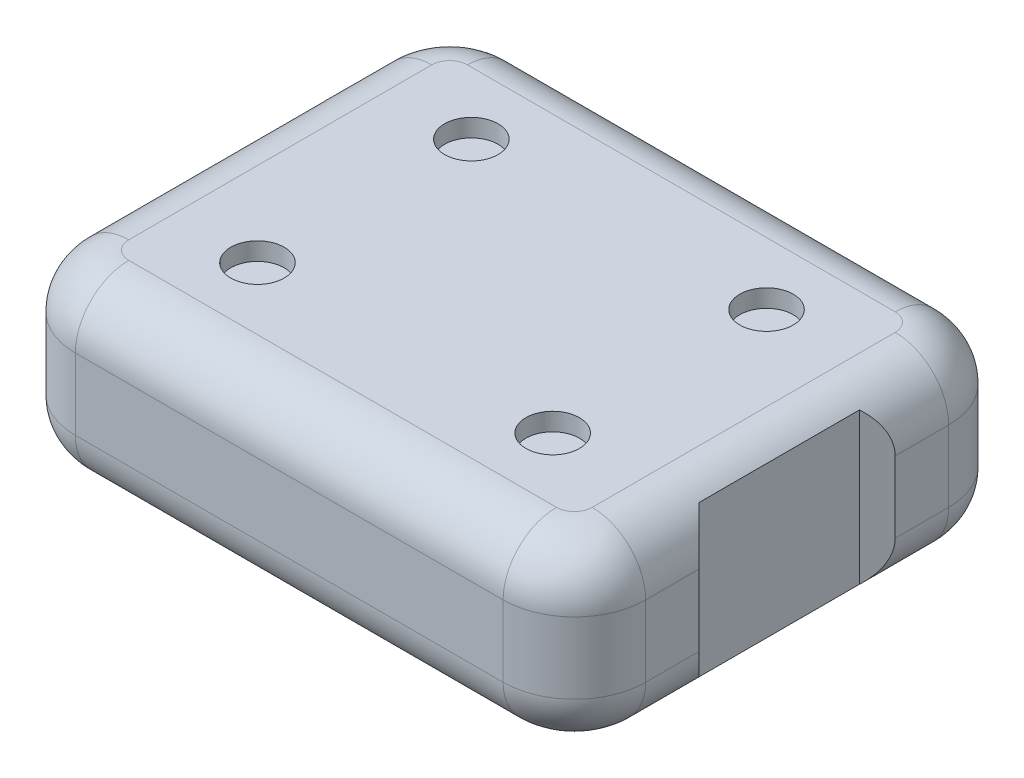
SolidWorks part; units mm, degrees
ref_plane "Front Plane" through (0, 0, 0) normal (0, 0, 1) x (1, 0, 0)
ref_plane "Top Plane" through (0, 0, 0) normal (0, 1, 0) x (1, 0, 0)
ref_plane "Right Plane" through (0, 0, 0) normal (1, 0, 0) x (0, 0, -1)
sketch "Sketch1" plane through (0, 0, 0) normal (0, 1, 0) x (1, 0, 0)
  line L0 (1.6, -1.25) -> (-1.6, 1.25) construction
  line L1 (-1.2, -1.25) -> (1.2, -1.25)
  line L2 (-1.6, -0.85) -> (-1.6, -0.55)
  line L3 (-1.2, 1.25) -> (1.2, 1.25)
  line L4 (1.6, -0.85) -> (1.6, -0.55)
  line L5 (1.5, -0.45) -> (1.6, -0.55)
  line L6 (-1.5, 0.45) -> (-1.5, -0.45)
  line L7 (1.5, 0.45) -> (1.6, 0.55)
  line L8 (-1.5, 0.45) -> (-1.6, 0.55)
  line L9 (1.5, 0.45) -> (1.5, -0.45)
  line L10 (-1.5, -0.45) -> (-1.6, -0.55)
  line L11 (1.5, 0) -> (0, 0) construction
  line L12 (0, 0) -> (-1.5, 0) construction
  line L13 (1.6, 0.55) -> (-1.6, 0.55) construction
  line L14 (1.6, 0.55) -> (1.6, 0.85)
  line L15 (-1.6, 0.55) -> (-1.6, 0.85)
  arc A0 (1.2, 1.25) -> (1.6, 0.85) centre (1.2, 0.85) cw
  arc A1 (1.6, -0.85) -> (1.2, -1.25) centre (1.2, -0.85) cw
  arc A2 (-1.2, -1.25) -> (-1.6, -0.85) centre (-1.2, -0.85) cw
  arc A3 (-1.6, 0.85) -> (-1.2, 1.25) centre (-1.2, 0.85) cw
  dimension "D3" = 0.4
  dimension "D1" = 3.2
  dimension "D2" = 2.5
  dimension "D4" = 0.9
  dimension "D5" = 1.1
  dimension "D6" = 0.1
extrude "Boss-Extrude1" add sketch "Sketch1" along normal blind 1
fillet "Fillet2" radius 0.3 16 edges at (-1.4828, 1, 1.1328) (0, 1, 1.25) (-1.6, 1, -0.7) (-1.4828, 1, -1.1328) (0, 1, -1.25) (1.4828, 1, -1.1328) (1.4828, 1, 1.1328) (1.6, 1, -0.7) (1.4828, 0, -1.1328) (-1.4828, 0, -1.1328) (-1.6, 0, 0.7) (-1.4828, 0, 1.1328) (1.6, 0, 0.7) (1.4828, 0, 1.1328) (0, 0, -1.25) (0, 0, 1.25)
sketch "Sketch2" plane through (0, 1, 0) normal (0, 1, 0) x (1, 0, 0)
  line L0 (0.8281, -0.6) -> (-0.8281, 0.6) construction
  line L1 (-0.8281, -0.6) -> (0.8281, -0.6) construction
  line L2 (-0.8281, -0.6) -> (-0.8281, 0.6) construction
  line L3 (-0.8281, 0.6) -> (0.8281, 0.6) construction
  line L4 (0.8281, -0.6) -> (0.8281, 0.6) construction
  line L5 (0.8281, -0.6) -> (1.2707, -0.9207) construction
  circle A0 centre (0.8281, 0.6) radius 0.15
  circle A1 centre (-0.8281, 0.6) radius 0.15
  circle A2 centre (-0.8281, -0.6) radius 0.15
  circle A3 centre (0.8281, -0.6) radius 0.15
  arc A4 (1.2, -0.95) -> (1.3, -0.85) centre (1.2, -0.85) ccw construction
  dimension "D1" = 0.3
  dimension "D2" = 1.2
extrude "Cut-Extrude1" cut sketch "Sketch2" against normal blind 0.1
